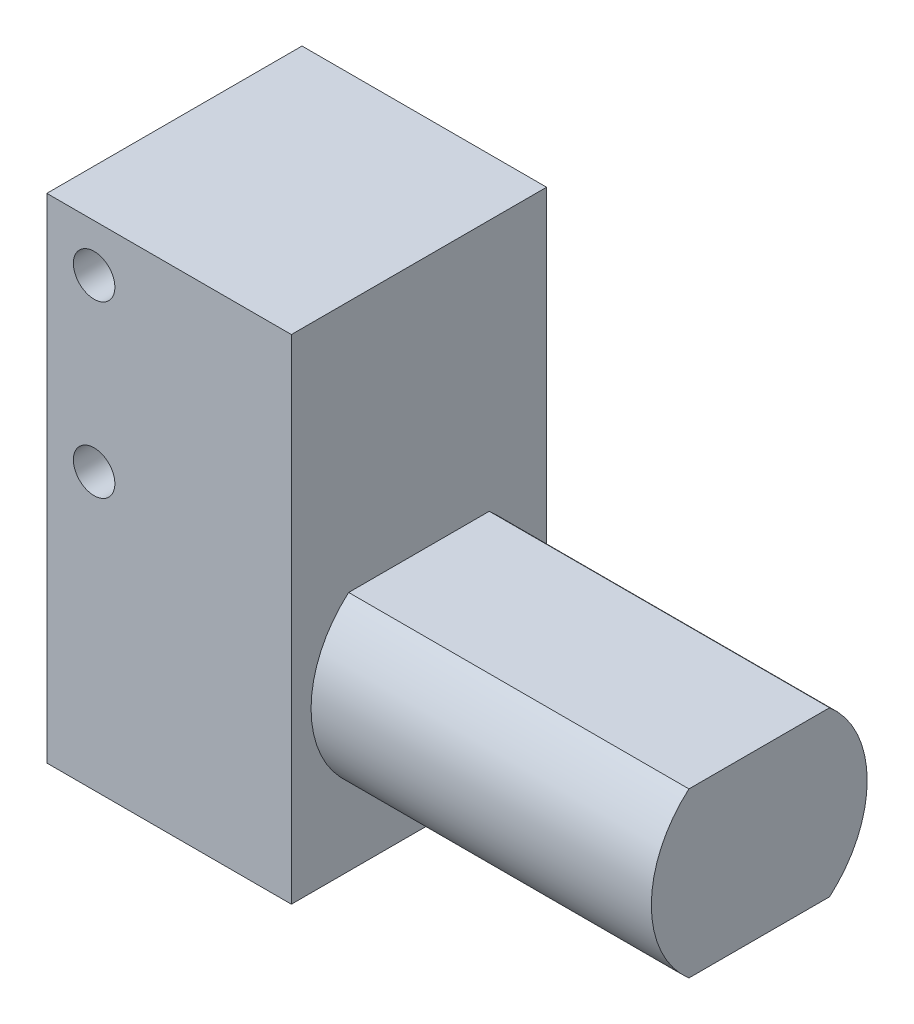
SolidWorks part; units mm, degrees
ref_plane "Front Plane" through (0, 0, 0) normal (0, 0, 1) x (1, 0, 0)
ref_plane "Top Plane" through (0, 0, 0) normal (0, 1, 0) x (1, 0, 0)
ref_plane "Right Plane" through (0, 0, 0) normal (1, 0, 0) x (0, 0, -1)
sketch "Sketch1" plane through (0, 0, 0) normal (0, 0, 1) x (1, 0, 0)
  line L1 (0, 0) -> (23, 0)
  line L2 (0, 0) -> (0, 46.4)
  line L3 (0, 46.4) -> (23, 46.4)
  line L4 (23, 0) -> (23, 46.4)
  dimension "D1" = 23
  dimension "D2" = 46.4
extrude "Boss-Extrude1" add sketch "Sketch1" along normal mid plane 24
sketch "Sketch6" plane through (0, 0, 12) normal (0, 0, 1) x (1, 0, 0)
  line L0 (23, 46.4) -> (0, 46.4) construction
  line L1 (11.5, 46.4) -> (11.5, 0) construction
  line L2 (0, 46.4) -> (0, 0) construction
  line L3 (0, 0) -> (23, 0) construction
  circle A0 centre (4.45, 41.95) radius 1.95
  circle A1 centre (4.45, 25.95) radius 1.95
  dimension "D1" = 3.9
  dimension "D2" = 2.5
  dimension "D3" = 2.5
  dimension "D4" = 16
  dimension "D5" = 14.1
extrude "Cut-Extrude1" cut sketch "Sketch6" against normal blind 5.5
mirror "Mirror1" about plane through (0, 0, 0) normal (0, 0, 1) of "Cut-Extrude1"
sketch "Sketch7" plane through (0, 0, 0) normal (-1, 0, 0) x (0, 0, 1)
  line L1 (12, 46.4) -> (-12, 46.4) construction
  circle A0 centre (0, 34.2) radius 2.7
  dimension "D1" = 5.4
  dimension "D2" = 9.5
  dimension "D3" = 14.9
extrude "Boss-Extrude2" add sketch "Sketch7" along normal blind 9
sketch "Sketch8" plane through (0, 0, 0) normal (0, 1, 0) x (1, 0, 0)
  line L0 (-9, 2.7) -> (-9, -2.7) construction
  line L1 (-9, 1.75) -> (-2, 1.75)
  line L2 (-9, 1.75) -> (-9, 2.7)
  line L3 (-9, 2.7) -> (-2, 2.7)
  line L4 (-2, 1.75) -> (-2, 2.7)
  line L7 (-9, -1.75) -> (-2, -1.75)
  line L8 (-9, -1.75) -> (-9, -2.7)
  line L9 (-9, -2.7) -> (-2, -2.7)
  line L10 (-2, -1.75) -> (-2, -2.7)
  line L13 (-9, -2.7) -> (0, -2.7) construction
  line L14 (0, 2.7) -> (-9, 2.7) construction
  dimension "D1" = 3.5
  dimension "D2" = 7
extrude "Cut-Extrude2" cut sketch "Sketch8" along normal through all
sketch "Sketch9" plane through (0, 0, 0) normal (-1, 0, 0) x (0, 0, 1)
  line L0 (0, -1000) -> (0, 49000) construction
  line L3 (12, 0) -> (-12, 0) construction
  circle A0 centre (-8, 10.45) radius 1.95
  circle A1 centre (8, 10.45) radius 1.95
  dimension "D1" = 3.9
  dimension "D3" = 8.5
  dimension "D2" = 16
extrude "Cut-Extrude3" cut sketch "Sketch9" against normal blind 5.5
sketch "Sketch10" plane through (23, 0, 0) normal (1, 0, 0) x (0, 0, -1)
  line L0 (-12, 0) -> (12, 0) construction
  circle A0 centre (0, 15) radius 10.15
  dimension "D1" = 15
  dimension "D2" = 20.3
extrude "Boss-Extrude3" add sketch "Sketch10" along normal blind 32
sketch "Sketch11" plane through (0, 0, 0) normal (0, 0, 1) x (1, 0, 0)
  line L0 (23, 0) -> (23, 46.4) construction
  line L1 (55, 25.15) -> (23, 25.15)
  line L2 (55, 25.15) -> (55, 22.7)
  line L3 (55, 22.7) -> (23, 22.7)
  line L4 (23, 25.15) -> (23, 22.7)
  line L5 (23, 4.85) -> (23, 25.15) construction
  line L6 (55, 4.85) -> (23, 4.85)
  line L7 (55, 4.85) -> (55, 7.3)
  line L8 (55, 7.3) -> (23, 7.3)
  line L9 (23, 4.85) -> (23, 7.3)
  dimension "D1" = 15.4
extrude "Cut-Extrude4" cut sketch "Sketch11" against normal through all both and the other way through all
sketch "Sketch12" plane through (0, 0, 0) normal (0, -1, 0) x (1, 0, 0)
  line L0 (23, 12) -> (23, -12) construction
  line L1 (13, 4.5) -> (16, 4.5)
  line L2 (13, 4.5) -> (13, -4.5)
  line L3 (13, -4.5) -> (16, -4.5)
  line L4 (16, 4.5) -> (16, -4.5)
  point P4 (13, 0)
  dimension "D1" = 3
  dimension "D2" = 9
  dimension "D3" = 7
extrude "Cut-Extrude5" cut sketch "Sketch12" against normal blind 5
equation "\"width\"= 24"
equation "\"thk\"= 3"
equation "\"holesize\"= 4.2"
equation "\"holedistance\"= ( 20 + 12 ) / 2"
equation "\"threaded_hole\"= 3.9"
equation "\"D4@Sketch6\"=\"holedistance\""
equation "\"D1@Sketch6\"=\"threaded_hole\""
equation "\"D2@Sketch9\"=\"holedistance\""
equation "\"D1@Sketch9\"=\"threaded_hole\""
